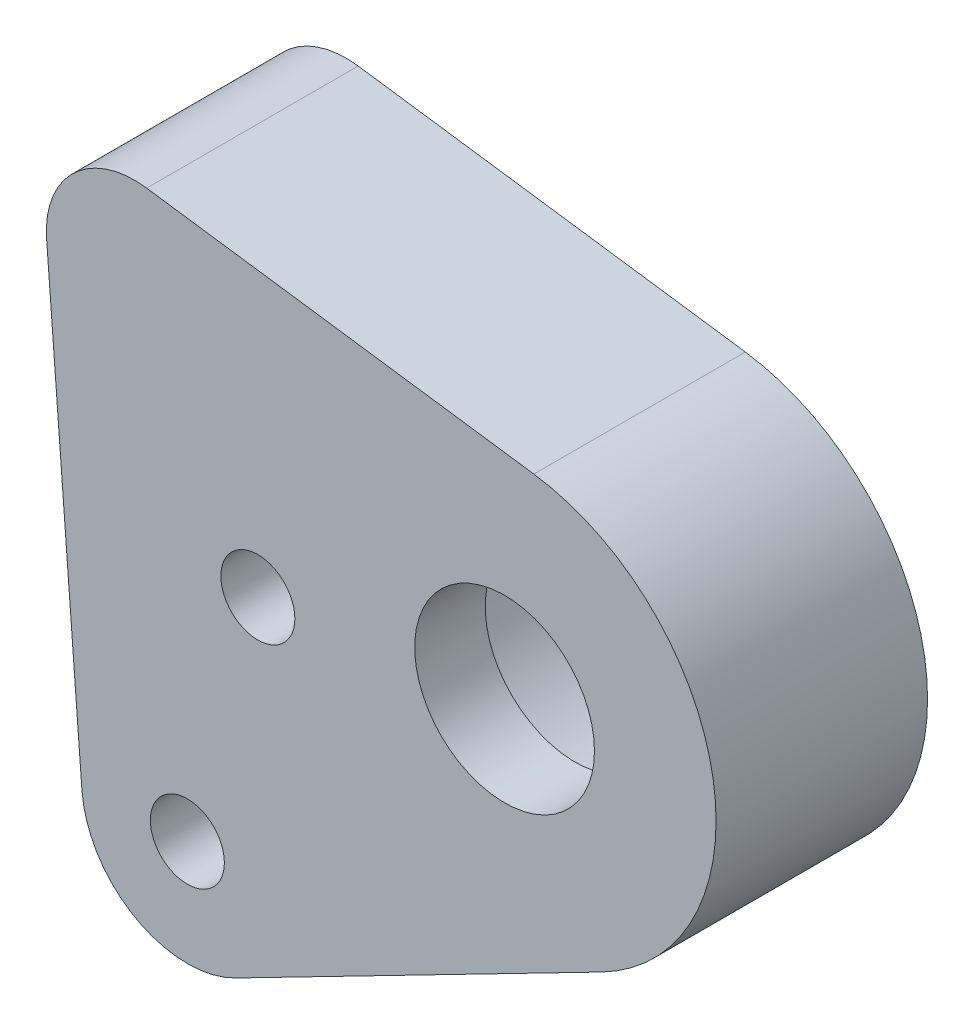
SolidWorks part; units mm, degrees
material "6061-T6 (SS)"
ref_plane "Alzado" through (0, 0, 0) normal (0, 0, 1) x (1, 0, 0)
ref_plane "Planta" through (0, 0, 0) normal (0, 1, 0) x (1, 0, 0)
ref_plane "Vista lateral" through (0, 0, 0) normal (1, 0, 0) x (0, 0, -1)
ref_plane "Plano1" through (0, 0, 54.4) normal (0, 0, 1) x (1, 0, 0)
sketch "Sk_Base_con_alojamiento_muelle" plane through (0, 0, 54.4) normal (0, 0, 1) x (1, 0, 0)
  line L0 (-31.9853, -16.3829) -> (-29.9824, -42.4595)
  line L1 (-21.2567, -47.3362) -> (-0.5135, -36.6723)
  line L2 (-4.3406, -14.1153) -> (-26.3086, -11.048)
  arc A0 (-29.9824, -42.4595) -> (-21.2567, -47.3362) centre (-24, -42) ccw
  arc A1 (-0.5135, -36.6723) -> (-4.3406, -14.1153) centre (-6, -26) ccw
  arc A2 (-26.3086, -11.048) -> (-31.9853, -16.3829) centre (-27, -16) ccw
  circle A3 centre (-6, -26) radius 9
  circle A4 centre (-20, -28) radius 2.1
  circle A5 centre (-24, -42) radius 2.1
extrude "Base_con_alojamiento_muelle" add sketch "Sk_Base_con_alojamiento_muelle" along normal blind 8
ref_plane "Plano2" through (0, 0, 62.4) normal (0, 0, 1) x (1, 0, 0)
sketch "Sk_Tapa" plane through (0, 0, 62.4) normal (0, 0, 1) x (1, 0, 0)
  line L0 (-31.9853, -16.3829) -> (-29.9824, -42.4595)
  line L1 (-21.2567, -47.3362) -> (-0.5135, -36.6723)
  line L2 (-4.3406, -14.1153) -> (-26.3086, -11.048)
  arc A0 (-29.9824, -42.4595) -> (-21.2567, -47.3362) centre (-24, -42) ccw
  arc A1 (-0.5135, -36.6723) -> (-4.3406, -14.1153) centre (-6, -26) ccw
  arc A2 (-26.3086, -11.048) -> (-31.9853, -16.3829) centre (-27, -16) ccw
  circle A3 centre (-6, -26) radius 5.1
  circle A4 centre (-20, -28) radius 2.1
  circle A5 centre (-24, -42) radius 2.1
extrude "Tapa" add sketch "Sk_Tapa" along normal blind 4
ref_plane "Plano3" through (-22.0388, 8.7292, 0) normal (-0.9297, 0.3683, 0) x (0, 0, -1)
sketch "Croquis1" plane through (-22.0388, 8.7292, 0) normal (-0.9297, 0.3683, 0) x (0, 0, -1)
  circle A2 centre (-60.633, 28.2858) radius 2.96
extrude "Cortar-Extruir1" cut sketch "Croquis1" against normal mid plane 41
thread "Rosca_M7x1" pitch 1 method cut profile "Perfil de rosca1" start angle 0, offset 11, length 11, pitch 1, diameter 5.92
ref_plane "Plano4" through (-23.6226, -21.0673, 63.593) normal (-0.3683, -0.9297, 0) x (0, 0, 1)
sketch "Perfil de rosca1" plane through (-23.6226, -21.0673, 63.593) normal (-0.3683, -0.9297, 0) x (0, 0, 1)
  line L0 (0, 0) -> (0, 1) construction
  line L1 (0, 0) -> (0.5413, 0.3125)
  line L2 (0.5413, 0.3125) -> (0.5413, 0.4375)
  line L3 (0.5413, 0.4375) -> (0, 0.75)
  line L4 (0.5413, 0.375) -> (0, 0.375) construction
  line L11 (0, 0) -> (0, 0.75)
  point P2 (0, 0)
  dimension "Pitch" = 1
  dimension "Profile_Angle" = 60
  dimension "Profile_Land" = 0.125
  dimension "Profile_Height" = 0.5413
